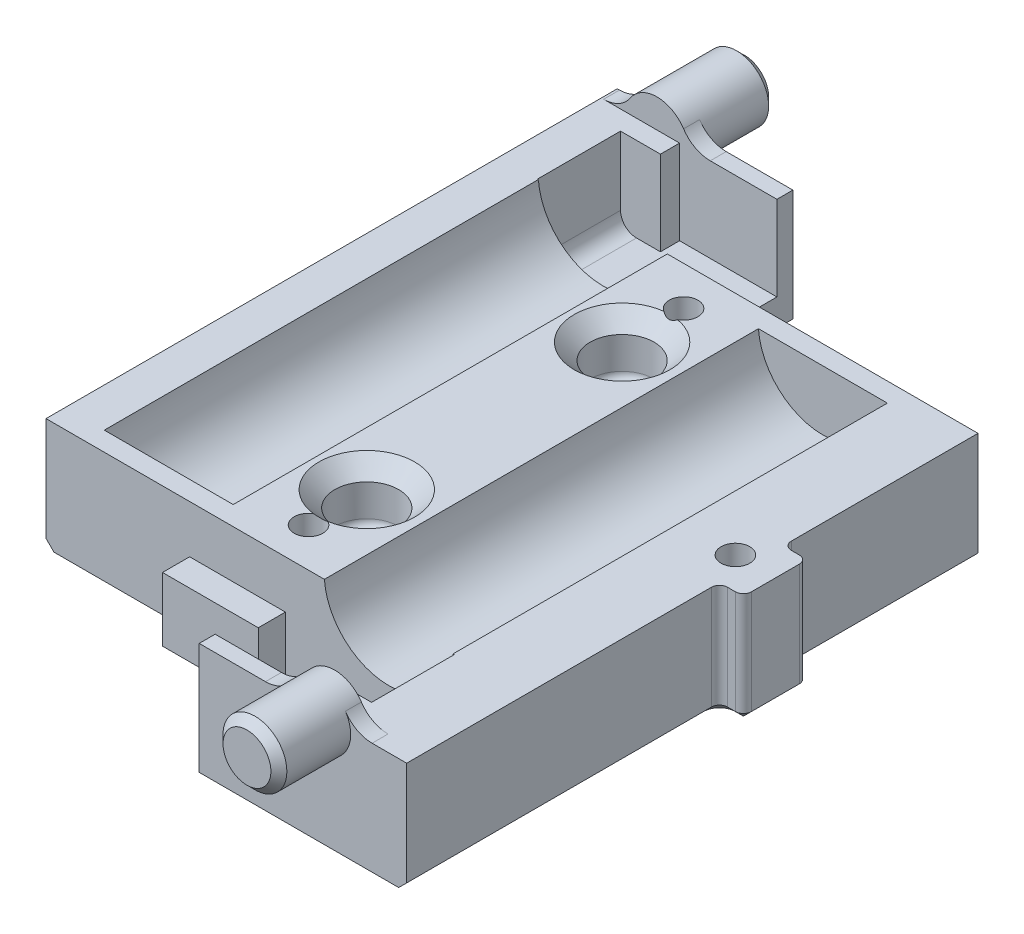
SolidWorks part; units mm, degrees
ref_plane "Front Plane" through (0, 0, 0) normal (0, 0, 1) x (1, 0, 0)
ref_plane "Top Plane" through (0, 0, 0) normal (0, 1, 0) x (1, 0, 0)
ref_plane "Right Plane" through (0, 0, 0) normal (1, 0, 0) x (0, 0, -1)
sketch "Sketch1" plane through (0, 0, 0) normal (0, 1, 0) x (1, 0, 0)
  line L1 (-61.4569, -66.3705) -> (-31.4569, -66.3705)
  line L2 (-61.4569, -66.3705) -> (-61.4569, -35.5705)
  line L3 (-61.4569, -35.5705) -> (-31.4569, -35.5705)
  line L4 (-31.4569, -66.3705) -> (-31.4569, -35.5705)
  dimension "D1" = 30.8
  dimension "D2" = 30
extrude "Boss-Extrude1" add sketch "Sketch1" along normal blind 7
sketch "Sketch2" plane through (0, 0, 0) normal (0, -1, 0) x (1, 0, 0)
  circle A0 centre (-47.4719, 50.9705) radius 4.05
  dimension "D1" = 8.1
extrude "Cut-Extrude1" cut sketch "Sketch2" against normal blind 6.5
sketch "Sketch3" plane through (0, 0, 0) normal (0, -1, 0) x (1, 0, 0)
  line L1 (-31.4569, 66.3705) -> (-46.4569, 66.3705)
  line L2 (-31.4569, 66.3705) -> (-31.4569, 65.1705)
  line L3 (-31.4569, 65.1705) -> (-46.4569, 65.1705)
  line L4 (-46.4569, 66.3705) -> (-46.4569, 65.1705)
  line L5 (-61.4569, 66.3705) -> (-52.4569, 66.3705)
  line L6 (-61.4569, 66.3705) -> (-61.4569, 65.1705)
  line L7 (-61.4569, 65.1705) -> (-52.4569, 65.1705)
  line L8 (-52.4569, 66.3705) -> (-52.4569, 65.1705)
  line L9 (-31.4569, 35.5705) -> (-42.4569, 35.5705)
  line L10 (-31.4569, 35.5705) -> (-31.4569, 36.7705)
  line L11 (-31.4569, 36.7705) -> (-42.4569, 36.7705)
  line L12 (-42.4569, 35.5705) -> (-42.4569, 36.7705)
  line L13 (-61.4569, 35.5705) -> (-48.4569, 35.5705)
  line L14 (-61.4569, 35.5705) -> (-61.4569, 36.7705)
  line L15 (-61.4569, 36.7705) -> (-48.4569, 36.7705)
  line L16 (-48.4569, 35.5705) -> (-48.4569, 36.7705)
  dimension "D1" = 15
  dimension "D2" = 9
  dimension "D3" = 1.2
  dimension "D4" = 1.2
  dimension "D5" = 1.2
  dimension "D6" = 1.2
  dimension "D7" = 11
  dimension "D8" = 13
extrude "Cut-Extrude2" cut sketch "Sketch3" against normal blind 4
sketch "Sketch4" plane through (0, 0, 66.3705) normal (0, 0, 1) x (1, 0, 0)
  line L1 (-61.4569, 7) -> (-31.4569, 7)
  line L2 (-61.4569, 7) -> (-61.4569, 4)
  line L3 (-61.4569, 4) -> (-31.4569, 4)
  line L4 (-31.4569, 7) -> (-31.4569, 4)
extrude "Cut-Extrude3" cut sketch "Sketch4" against normal blind 1.2
sketch "Sketch5" plane through (0, 0, 35.5705) normal (0, 0, -1) x (-1, 0, 0)
  line L1 (61.4569, 4) -> (31.4569, 4)
  line L2 (61.4569, 4) -> (61.4569, 7)
  line L3 (61.4569, 7) -> (31.4569, 7)
  line L4 (31.4569, 4) -> (31.4569, 7)
extrude "Cut-Extrude4" cut sketch "Sketch5" against normal blind 1.2
sketch "Sketch6" plane through (0, 0, 65.1705) normal (0, 0, 1) x (1, 0, 0)
  line L0 (-44.0746, 7.3) -> (-35.8746, 7.3) construction
  circle A0 centre (-39.9746, 7.3) radius 4.05
  dimension "D1" = 8.1
extrude "Cut-Extrude5" cut sketch "Sketch6" against normal blind 27.2
sketch "Sketch7" plane through (0, 0, 36.7705) normal (0, 0, -1) x (-1, 0, 0)
  line L0 (50.8646, 7.3) -> (59.0646, 7.3) construction
  circle A0 centre (54.9646, 7.3) radius 4.05
  dimension "D1" = 8.1
extrude "Cut-Extrude6" cut sketch "Sketch7" against normal blind 27.2
sketch "Sketch10" plane through (0, 0, 65.1705) normal (0, 0, 1) x (1, 0, 0)
  line L5 (-31.4569, 0) -> (-31.4569, 7)
  line L6 (-31.4569, 7) -> (-35.8569, 7)
  line L7 (-31.4569, 7) -> (-35.9357, 7) construction
  line L8 (-35.8569, 7) -> (-35.8569, 1.7)
  line L9 (-35.8569, 1.7) -> (-44.4569, 1.7)
  line L10 (-44.4569, 1.7) -> (-44.4569, 0)
  line L11 (-46.4569, 0) -> (-31.4569, 0) construction
  line L12 (-44.4569, 0) -> (-31.4569, 0)
  dimension "D1" = 4.4
  dimension "D2" = 1.7
  dimension "D3" = 13
extrude "Boss-Extrude2" add sketch "Sketch10" along normal blind 6.4
fillet "Fillet1" radius 1 1 edges at (-35.8569, 1.7, 68.3705)
sketch "Sketch11" plane through (0, 0, 36.7705) normal (0, 0, -1) x (-1, 0, 0)
  line L0 (61.4569, 7) -> (61.4569, 0)
  line L1 (61.4569, 0) -> (50.4569, 0)
  line L2 (48.4569, 0) -> (61.4569, 0) construction
  line L3 (50.4569, 0) -> (50.4569, 1.7)
  line L4 (50.4569, 1.7) -> (59.0569, 1.7)
  line L5 (59.0569, 1.7) -> (59.0569, 7)
  line L6 (61.4569, 7) -> (59.0034, 7) construction
  line L7 (59.0569, 7) -> (61.4569, 7)
  dimension "D1" = 2.4
  dimension "D2" = 1.7
  dimension "D3" = 11
extrude "Boss-Extrude3" add sketch "Sketch11" along normal blind 6.4
fillet "Fillet2" radius 1 1 edges at (-59.0569, 1.7, 33.5705)
sketch "Sketch13" plane through (0, 0, 71.5705) normal (0, 0, 1) x (1, 0, 0)
  line L0 (-44.0134, 7) -> (-61.4569, 7) construction
  line L1 (-31.4569, 0) -> (-44.4569, 0)
  line L2 (-31.4569, 0) -> (-31.4569, 7)
  line L3 (-31.4569, 7) -> (-44.4569, 7)
  line L4 (-44.4569, 0) -> (-44.4569, 7)
extrude "Boss-Extrude4" add sketch "Sketch13" along normal blind 1
sketch "Sketch14" plane through (0, 0, 30.3705) normal (0, 0, -1) x (-1, 0, 0)
  line L0 (50.9257, 7) -> (31.4569, 7) construction
  line L1 (61.4569, 0) -> (50.4569, 0)
  line L2 (61.4569, 0) -> (61.4569, 7)
  line L3 (61.4569, 7) -> (50.4569, 7)
  line L4 (50.4569, 0) -> (50.4569, 7)
extrude "Boss-Extrude5" add sketch "Sketch14" along normal blind 1
sketch "Sketch15" plane through (0, 0, 71.5705) normal (0, 0, 1) x (1, 0, 0)
  circle A0 centre (-36.9646, 6.8) radius 2
  dimension "D1" = 4
sketch "Sketch16" plane through (0, 0, 30.3705) normal (0, 0, -1) x (-1, 0, 0)
  circle A0 centre (57.9746, 6.8) radius 2
  dimension "D1" = 4
extrude "Boss-Extrude8" add sketch "Sketch15" along normal blind 5.5
extrude "Boss-Extrude9" add sketch "Sketch16" along normal blind 5.5
fillet "Fillet3" radius 2 1 edges at (-59.9645, 7, 29.8705)
fillet "Fillet4" radius 2 1 edges at (-55.9846, 7, 29.8705)
fillet "Fillet5" radius 2 2 edges at (-34.9746, 7, 72.0705) (-38.9545, 7, 72.0705)
chamfer "Chamfer2" distance 0.5 angle 45 1 edges at (-34.9646, 6.8, 77.0705)
chamfer "Chamfer3" distance 0.5 angle 45 1 edges at (-59.9746, 6.8, 24.8705)
sketch "Sketch17" plane through (-31.4569, 0, 0) normal (1, 0, 0) x (0, 0, -1)
  line L0 (-72.5705, 7) -> (-36.7705, 7) construction
  line L1 (-52.9705, 7) -> (-48.9705, 7)
  line L2 (-52.9705, 7) -> (-52.9705, 0)
  line L3 (-52.9705, 0) -> (-48.9705, 0)
  line L4 (-48.9705, 7) -> (-48.9705, 0)
  line L5 (-72.5705, 0) -> (-36.7705, 0) construction
  line L6 (-36.7705, 7) -> (-36.7705, 0) construction
  dimension "D1" = 4
  dimension "D2" = 12.2
extrude "Boss-Extrude10" add sketch "Sketch17" along normal blind 1.5
fillet "Fillet7" radius 0.5 4 edges at (-31.4569, 3.5, 52.9705) (-29.9569, 3.5, 52.9705) (-29.9569, 3.5, 48.9705) (-31.4569, 3.5, 48.9705)
sketch "Sketch18" plane through (0, 0, 0) normal (0, -1, 0) x (1, 0, 0)
  circle A0 centre (-32.4569, 50.9705) radius 0.9
  dimension "D1" = 1.8
extrude "Cut-Extrude9" cut sketch "Sketch18" against normal through all
sketch "Sketch19" plane through (0, 0, 0) normal (0, -1, 0) x (1, 0, 0)
  circle A0 centre (-32.4569, 50.9705) radius 1.6
  dimension "D1" = 3.2
extrude "Cut-Extrude10" cut sketch "Sketch19" against normal blind 2
sketch "Sketch20" plane through (0, 0, 0) normal (0, -1, 0) x (1, 0, 0)
  circle A0 centre (-47.4569, 62.7205) radius 0.9
  circle A1 centre (-47.4569, 39.2205) radius 0.9
  dimension "D1" = 1.8
  dimension "D2" = 1.8
extrude "Cut-Extrude11" cut sketch "Sketch20" against normal through all
sketch "Sketch21" plane through (0, 0, 0) normal (0, -1, 0) x (1, 0, 0)
  circle A0 centre (-47.4569, 62.7205) radius 1.6
  circle A1 centre (-47.4569, 39.2205) radius 1.6
  dimension "D1" = 3.2
  dimension "D2" = 3.2
extrude "Cut-Extrude12" cut sketch "Sketch21" against normal blind 2
chamfer "Chamfer6" distance 0.5 angle 45 9 edges at (-61.4569, 0, 47.2705) (-31.3104, 0, 48.8241) (-30.7069, 0, 48.9705) (-30.1033, 0, 49.117) (-29.9569, 0, 50.9705) (-30.1033, 0, 52.8241) (-30.7069, 0, 52.9705) (-31.3104, 0, 53.117) (-31.4569, 0, 42.6205)
sketch "Sketch22" plane through (0, 0, 35.5705) normal (0, 0, -1) x (-1, 0, 0)
  line L1 (42.4569, 4) -> (48.4569, 4)
  line L2 (42.4569, 4) -> (42.4569, 0)
  line L3 (42.4569, 0) -> (48.4569, 0)
  line L4 (48.4569, 4) -> (48.4569, 0)
extrude "Boss-Extrude11" add sketch "Sketch22" along normal blind 0.5
sketch "Sketch23" plane through (0, 0, 66.3705) normal (0, 0, 1) x (1, 0, 0)
  line L1 (-52.4569, 4) -> (-46.4569, 4)
  line L2 (-52.4569, 4) -> (-52.4569, 0)
  line L3 (-52.4569, 0) -> (-46.4569, 0)
  line L4 (-46.4569, 4) -> (-46.4569, 0)
extrude "Boss-Extrude12" add sketch "Sketch23" along normal blind 0.5
sketch "Sketch24" plane through (0, 7, 0) normal (0, 1, 0) x (1, 0, 0)
  line L0 (-35.8569, -65.1705) -> (-35.8569, -71.5705) construction
  line L1 (-33.6239, -71.5705) -> (-38.3569, -71.5705)
  line L2 (-33.6239, -71.5705) -> (-33.6239, -70.3705)
  line L3 (-33.6239, -70.3705) -> (-38.3569, -70.3705)
  line L4 (-38.3569, -71.5705) -> (-38.3569, -70.3705)
  line L5 (-59.0569, -36.7705) -> (-59.0569, -30.3705) construction
  line L6 (-61.3152, -30.3705) -> (-56.5569, -30.3705)
  line L7 (-61.3152, -30.3705) -> (-61.3152, -31.5705)
  line L8 (-61.3152, -31.5705) -> (-56.5569, -31.5705)
  line L9 (-56.5569, -30.3705) -> (-56.5569, -31.5705)
  dimension "D1" = 1.2
  dimension "D2" = 2.5
  dimension "D3" = 1.2
  dimension "D4" = 2.5
extrude "Boss-Extrude13" add sketch "Sketch24" against normal up to surface (5.3 mm away) up to face at (-54.2569, 1.7, 33.5705)
sketch "Sketch25" plane through (0, 0, 0) normal (0, -1, 0) x (1, 0, 0)
  circle A0 centre (-47.4719, 50.9705) radius 4.05
extrude "Boss-Extrude14" add sketch "Sketch25" against normal up to surface (7 mm away) up to face at (-47.4569, 7, 61.8205)
sketch "Sketch26" plane through (0, 0, 37.9705) normal (0, 0, 1) x (1, 0, 0)
  circle A0 centre (-39.9746, 7.3) radius 4.05
extrude "Cut-Extrude13" cut sketch "Sketch26" along normal up to surface (27.2 mm away) up to face at (-47.066, 2.7602, 65.1705)
sketch "Sketch27" plane through (0, 0, 63.9705) normal (0, 0, -1) x (-1, 0, 0)
  circle A0 centre (54.9646, 7.3) radius 4.05
extrude "Cut-Extrude14" cut sketch "Sketch27" along normal up to surface (27.2 mm away) up to face at (-47.4228, 2.7602, 36.7705)
sketch "Sketch28" plane through (0, 0, 0) normal (0, -1, 0) x (1, 0, 0)
  circle A0 centre (-47.5569, 58.9705) radius 0.8
  circle A1 centre (-47.5569, 42.9705) radius 0.8
  dimension "D1" = 1.6
  dimension "D2" = 1.6
extrude "Cut-Extrude15" cut sketch "Sketch28" against normal through all
sketch "Sketch30" plane through (0, 7, 0) normal (0, 1, 0) x (1, 0, 0)
  circle A0 centre (-47.5569, -42.9705) radius 1.15
  circle A1 centre (-47.5569, -58.9705) radius 1.15
  dimension "D1" = 2.3
  dimension "D2" = 2.3
extrude "Cut-Extrude16" cut sketch "Sketch30" against normal blind 4.7 contours A0
sketch "Sketch32" plane through (0, 7, 0) normal (0, 1, 0) x (1, 0, 0)
  circle A0 centre (-47.5569, -58.9705) radius 1.15
  dimension "D1" = 2.3
extrude "Cut-Extrude17" cut sketch "Sketch32" against normal blind 4.7
sketch "Sketch33" plane through (0, 7, 0) normal (0, 1, 0) x (1, 0, 0)
  circle A0 centre (-47.5569, -58.9705) radius 2
  circle A1 centre (-47.5569, -42.9705) radius 2
  dimension "D1" = 4
  dimension "D2" = 4
extrude "Cut-Extrude18" cut sketch "Sketch33" against normal blind 3.5
fillet "Fillet8" radius 0.5 2 edges at (-47.5569, 3.5, 44.9705) (-47.5569, 3.5, 60.9705)
chamfer "Chamfer7" distance 1 angle 45 2 edges at (-47.5569, 7, 44.9705) (-47.5569, 7, 60.9705)
